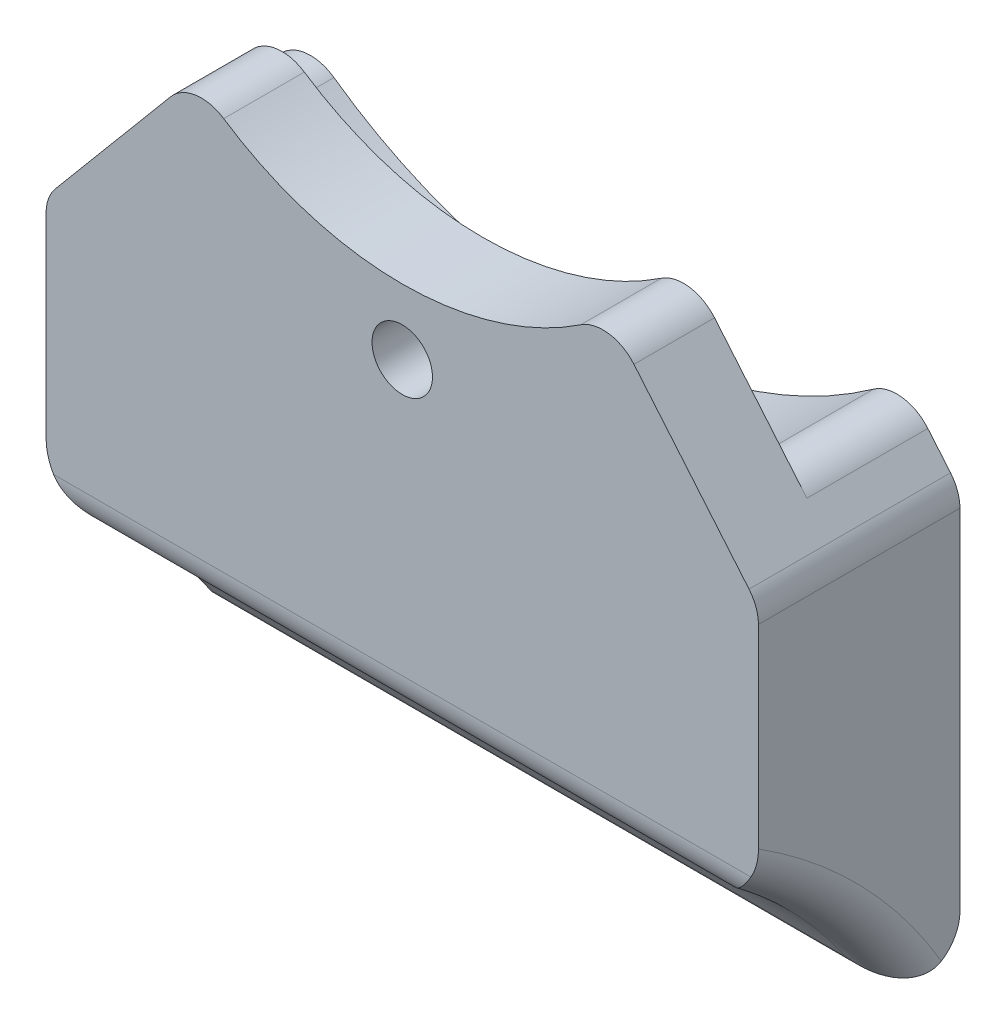
SolidWorks part; units mm, degrees
ref_plane "前视基准面" through (0, 0, 0) normal (0, 0, 1) x (1, 0, 0)
ref_plane "上视基准面" through (0, 0, 0) normal (0, 1, 0) x (1, 0, 0)
ref_plane "右视基准面" through (0, 0, 0) normal (1, 0, 0) x (0, 0, -1)
other "Configuration Table"
sketch "草图1" plane through (0, 0, 0) normal (0, 0, 1) x (1, 0, 0)
  line L0 (0, 0) -> (0, -23.1) construction
  line L1 (-10.2846, -12.2567) -> (-14.8484, -17.6956)
  line L2 (10.2846, -12.2567) -> (14.8484, -17.6956)
  circle A0 centre (0, -19.25) radius 1.5
  circle A1 centre (0, 0) radius 23.1
  circle A2 centre (0, 0) radius 16
  dimension "D1" = 3
  dimension "D3" = 46.2
  dimension "D4" = 32
  dimension "D2" = 19.25
  dimension "D5" = 80
extrude "凸台-拉伸1" add sketch "草图1" along normal blind 4 contours A2 L0 A0 A1 L2 | L0 A2 L1 A1 A0 region at (6.8502, -18.1582, 0) region at (-6.8502, -18.1582, 0)
sketch "草图3" plane through (0, 0, 4) normal (0, 0, 1) x (1, 0, 0)
  line L0 (-14.8484, -17.6956) -> (-17.6767, -21.0662)
  line L1 (14.8484, -17.6956) -> (17.6767, -21.0662)
  line L2 (-10.2846, -12.2567) -> (-14.8484, -17.6956)
  line L3 (14.8484, -17.6956) -> (10.2846, -12.2567)
  line L4 (-10.2846, -12.2567) -> (-14.8484, -17.6956)
  line L5 (14.8484, -17.6956) -> (10.2846, -12.2567)
  circle A0 centre (0, 0) radius 27.5
  arc A2 (-10.2846, -12.2567) -> (10.2846, -12.2567) centre (0, 0) ccw
  arc A3 (-14.8484, -17.6956) -> (14.8484, -17.6956) centre (0, 0) ccw
  arc A4 (-10.2846, -12.2567) -> (10.2846, -12.2567) centre (0, 0) ccw
  arc A5 (-14.8484, -17.6956) -> (14.8484, -17.6956) centre (0, 0) ccw
  arc M8 (-14.8484, -17.6956) -> (14.8484, -17.6956) centre (0, 0) ccw
  dimension "D2" = 55
  dimension "D1" = 0
extrude "凸台-拉伸2" add sketch "草图3" against normal blind 10 contours L0 A0 L1 M8 region at (0, -23.3531, 4)
sketch "草图4" plane through (0, 0, 4) normal (0, 0, 1) x (1, 0, 0)
  line L0 (-17.6767, -21.0662) -> (-17.6767, -51.0662)
  line L1 (-17.6767, -51.0662) -> (17.6767, -51.0662)
  line L2 (-10.2846, -12.2567) -> (-17.6767, -21.0662)
  line L3 (17.6767, -21.0662) -> (10.2846, -12.2567)
  line L4 (-10.2846, -12.2567) -> (-17.6767, -21.0662)
  line L5 (17.6767, -21.0662) -> (10.2846, -12.2567)
  line L6 (17.6767, -51.0662) -> (17.6767, -21.0662)
  arc A2 (-10.2846, -12.2567) -> (10.2846, -12.2567) centre (0, 0) ccw
  arc A3 (-17.6767, -21.0662) -> (17.6767, -21.0662) centre (0, 0) ccw
  arc A4 (-10.2846, -12.2567) -> (10.2846, -12.2567) centre (0, 0) ccw
  arc A5 (-17.6767, -21.0662) -> (17.6767, -21.0662) centre (0, 0) ccw
  arc M9 (-17.6767, -21.0662) -> (17.6767, -21.0662) centre (0, 0) ccw
  dimension "D2" = 30
  dimension "D1" = 0
extrude "凸台-拉伸3" add sketch "草图4" against normal blind 10 contours L1 L6 L0 M9 region at (0, -38.1977, 4)
sketch "草图7" plane through (17.6767, 0, 0) normal (1, 0, 0) x (0, 0, -1)
  line L3 (6, -51.0662) -> (6, -21.0662) construction
  line L6 (-4, -21.0662) -> (-4, -51.0662)
  line L7 (-4, -51.0662) -> (6, -51.0662)
  line L8 (6, -51.0662) -> (6, -21.0662)
  line L9 (6, -21.0662) -> (-4, -21.0662)
  line L10 (-4, -21.0662) -> (-4, -51.0662)
  line L11 (-4, -51.0662) -> (6, -51.0662)
  line L12 (6, -51.0662) -> (6, -21.0662)
  line L13 (6, -21.0662) -> (-4, -21.0662)
  arc A1 (-4, -33.85) -> (6, -48.0619) centre (-18.7914, -54.8819) cw
  point P0 (-4, -33.85)
  point P6 (6, -47.9533)
  point P8 (6, -42.344)
  point P13 (6, -42.344)
  point P14 (6, -42.344)
  point P15 (0, 0)
  point P17 (6, -46.3147)
  line M6 (-4, -51.0662) -> (6, -51.0662)
  line M7 (6, -51.0662) -> (6, -21.0662)
  dimension "D1" = 0
extrude "切除-拉伸1" cut sketch "草图7" against normal through all contours L10 M6 M7 region at (17.6767, -44.4999, -0.0762)
fillet "圆角1" radius 2 10 edges at (14.8484, -17.6956, -3) (-14.8484, -17.6956, -3) (-17.6767, -21.0662, -1) (10.2846, -12.2567, 2) (17.6767, -21.0662, -1) (-10.2846, -12.2567, 2) (0, -48.0619, -6) (-17.6767, -40.0856, -2.237) (0, -33.85, 4) (17.6767, -40.0856, -2.237)
